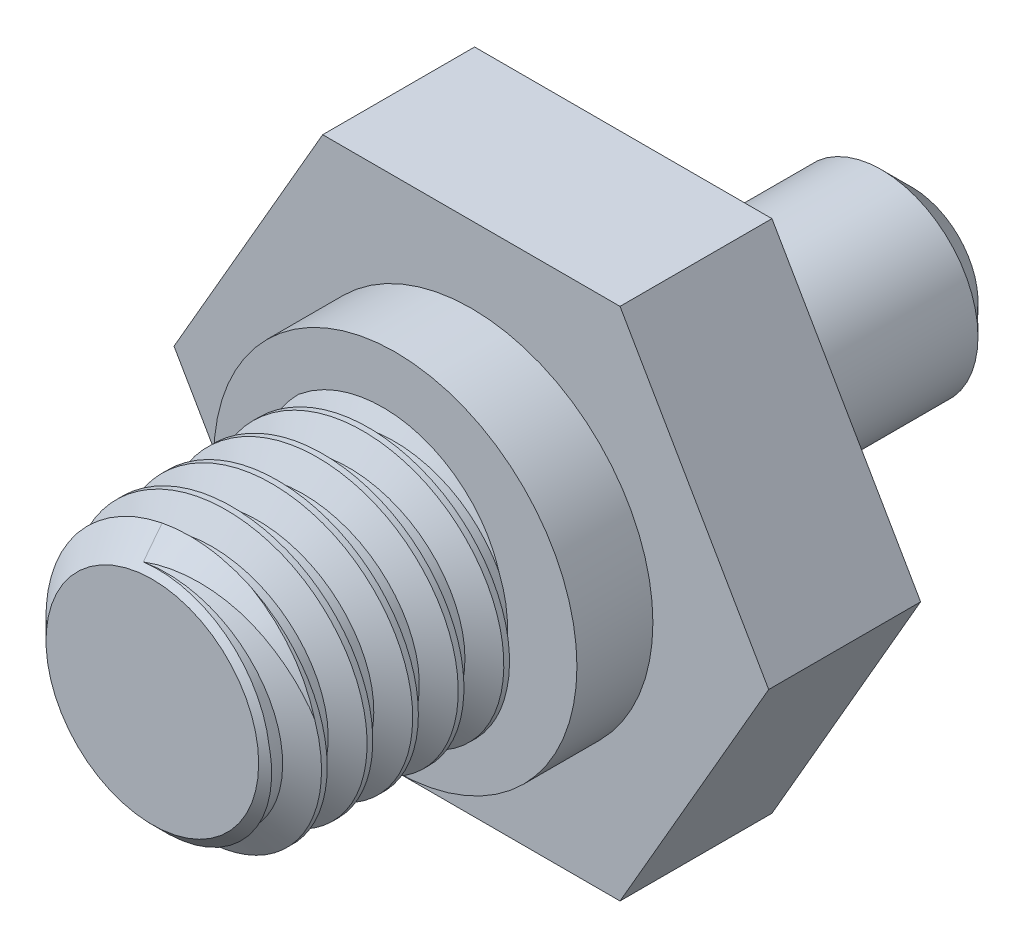
SolidWorks part; units mm, degrees
material "6061 Alloy"
ref_plane "Front Plane" through (0, 0, 0) normal (0, 0, 1) x (1, 0, 0)
ref_plane "Top Plane" through (0, 0, 0) normal (0, 1, 0) x (1, 0, 0)
ref_plane "Right Plane" through (0, 0, 0) normal (1, 0, 0) x (0, 0, -1)
sketch "Sketch1" plane through (0, 0, 0) normal (0, 0, 1) x (1, 0, 0)
  line L1 (4.893, 8.475) -> (-4.893, 8.475)
  line L2 (-4.893, 8.475) -> (-9.7861, 0)
  line L3 (-9.7861, 0) -> (-4.893, -8.475)
  line L4 (-4.893, -8.475) -> (4.893, -8.475)
  line L5 (4.893, -8.475) -> (9.7861, 0)
  line L6 (9.7861, 0) -> (4.893, 8.475)
  circle A0 centre (0, 0) radius 8.475 construction
  dimension "D1" = 16.95
extrude "Boss-Extrude1" add sketch "Sketch1" along normal blind 5
sketch "Sketch4" plane through (0, 0, 5) normal (0, 0, 1) x (1, 0, 0)
  circle A0 centre (0, 0) radius 5.975
  dimension "D1" = 11.95
extrude "Boss-Extrude3" add sketch "Sketch4" along normal blind 2.5
sketch "Sketch2" plane through (0, 0, 5) normal (0, 0, 1) x (1, 0, 0)
  circle A0 centre (0, 0) radius 4.5
  dimension "D1" = 9
extrude "Boss-Extrude2" add sketch "Sketch2" along normal blind 8 from surface starting at face at (5.975, 0, 7.5)
chamfer "Chamfer1" distance 1 angle 45 1 edges at (4.5, 0, 15.5)
thread "Thread2" pitch 1.5 method cut trim with end face yes profile "Thread Profile2" start angle 0, offset 2, length 0, pitch 1.5, diameter 9
ref_plane "Plane2" through (-4.5, 0, 16.5) normal (0, -1, 0) x (-1, 0, 0)
sketch "Thread Profile2" plane through (-4.5, 0, 16.5) normal (0, -1, 0) x (-1, 0, 0)
  line L0 (0, 0) -> (0, 1.5) construction
  line L11 (0, 0) -> (0, 1.3125)
  line L12 (0, 1.3125) -> (-0.8119, 0.8437)
  line L13 (-0.8119, 0.8437) -> (-0.8119, 0.4687)
  line L15 (-0.8119, 0.4687) -> (0, 0)
  line L17 (-0.8119, 0.6562) -> (0, 0.6562) construction
  point P2 (0, 0)
  dimension "Pitch" = 1.5
  dimension "Profile_Angle" = 60
  dimension "Profile_Land" = 0.375
  dimension "Profile_Height" = 0.8119
ref_axis "Axis1" through (0, 0, -29.5358) along (0, 0, 1)
sketch "Sketch5" plane through (0, 0, 0) normal (0, 0, -1) x (-1, 0, 0)
  circle A0 centre (0, 0) radius 3.175
  dimension "D1" = 6.35
extrude "Boss-Extrude4" add sketch "Sketch5" along normal blind 9.5
chamfer "Chamfer2" distance 1 angle 45 1 edges at (-3.175, 0, -9.5)
fillet "Fillet1" radius 1 1 edges at (-3.175, 0, 0)
